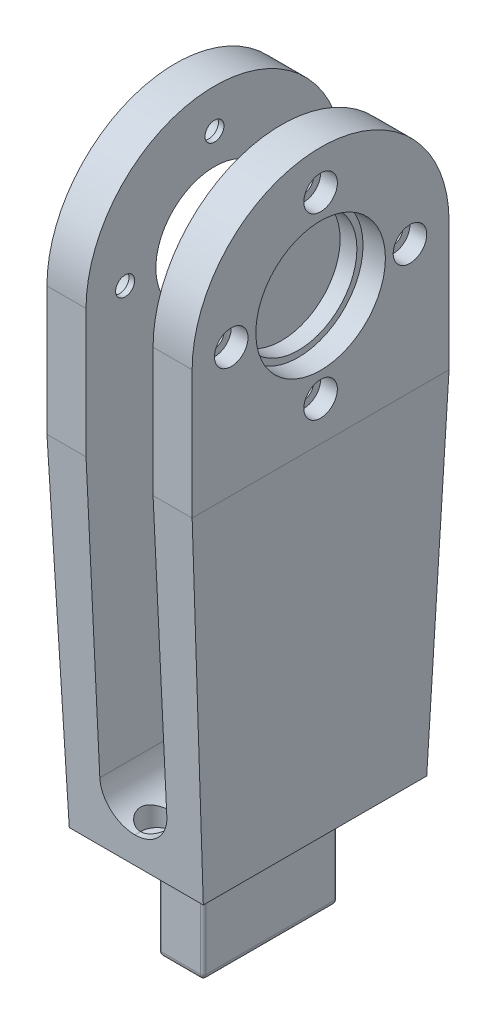
SolidWorks part; units mm, degrees
ref_plane "Front Plane" through (0, 0, 0) normal (0, 0, 1) x (1, 0, 0)
ref_plane "Top Plane" through (0, 0, 0) normal (0, 1, 0) x (1, 0, 0)
ref_plane "Right Plane" through (0, 0, 0) normal (1, 0, 0) x (0, 0, -1)
ref_plane "Plane1" through (6, 0, 0) normal (1, 0, 0) x (0, 0, -1)
sketch "Sketch2" plane through (6, 0, 0) normal (1, 0, 0) x (0, 0, -1)
  line L0 (0, 16) -> (0, 0) construction
  circle A0 centre (0, 0) radius 23
  circle A1 centre (0, 16) radius 1.7
  circle A2 centre (16, 0) radius 1.7
  circle A3 centre (0, -16) radius 1.7
  circle A4 centre (-16, 0) radius 1.7
  point P14 (0, 0)
  dimension "D1" = 46
  dimension "D2" = 3.4
  dimension "D3" = 16
  dimension "D4" = 4
extrude "Boss-Extrude1" add sketch "Sketch2" along normal blind 7
ref_plane "Plane2" through (0, -23, 0) normal (0, -1, 0) x (-1, 0, 0)
sketch "Sketch7" plane through (0, -23, 0) normal (0, -1, 0) x (-1, 0, 0)
  line L0 (-13, -23) -> (-6, -23) construction
  line L1 (-6, -23) -> (-6, 23) construction
  line L2 (-6, 23) -> (-13, 23) construction
  line L4 (-13, -23) -> (-6, -23)
  line L5 (-6, -23) -> (-6, 23)
  line L6 (-6, 23) -> (-13, 23)
  line L8 (-13, 23) -> (-13, -23)
  dimension "D1" = 7
ref_plane "Plane3" through (0, -85, 0) normal (0, 1, 0) x (1, 0, 0)
sketch "Sketch8" plane through (0, -85, 0) normal (0, 1, 0) x (1, 0, 0)
  line L0 (0, 0) -> (-31.8986, 0) construction
  line L2 (6, 20) -> (12, 20)
  line L3 (6, 20) -> (6, -20)
  line L4 (6, -20) -> (12, -20)
  line L5 (12, 20) -> (12, -20)
  line L6 (6, 20) -> (12, -20) construction
  line L7 (6, -20) -> (12, 20) construction
  line L8 (6, -23) -> (6, 23) construction
  point P3 (9, 0)
  dimension "D1" = 6
  dimension "D2" = 40
loft "Loft2" add profiles "Sketch7", "Sketch8"
sketch "Sketch16" plane through (0, -23, 0) normal (0, 1, 0) x (1, 0, 0)
  line L4 (6, 23) -> (6, -23)
  line L5 (6, -23) -> (13, -23)
  line L6 (13, -23) -> (13, 23)
  line L7 (13, 23) -> (6, 23)
  line L8 (6, 23) -> (6, -23)
  line L9 (6, -23) -> (13, -23)
  line L10 (13, -23) -> (13, 23)
  line L11 (13, 23) -> (6, 23)
  dimension "D1" = 0
extrude "Boss-Extrude7" add sketch "Sketch16" along normal up to surface up to face at (13, 0, -23)
sketch "Sketch19" plane through (6, 0, 0) normal (-1, 0, 0) x (0, 0, 1)
  line L0 (-20.2419, -80) -> (20.2419, -80)
  line L1 (-23, -23) -> (-20, -85) construction
  line L2 (23, -23) -> (20, -85) construction
  line L3 (-20, -85) -> (20, -85) construction
  line L4 (20.2419, -80) -> (20, -85)
  line L5 (-20.2419, -80) -> (-20, -85)
  line L6 (-20, -85) -> (20, -85)
  dimension "D1" = 5
extrude "Boss-Extrude8" add sketch "Sketch19" along normal up to surface (6 mm away) up to plane "Right Plane"
sketch "Sketch20" plane through (13, 0, 0) normal (1, 0, 0) x (0, 0, -1)
  circle A0 centre (0, 0) radius 11.6
  dimension "D1" = 23.2
extrude "Cut-Extrude1" cut sketch "Sketch20" against normal blind 4
sketch "Sketch21" plane through (9, 0, 0) normal (1, 0, 0) x (0, 0, -1)
  circle A0 centre (0, 0) radius 10.5
  dimension "D1" = 21
extrude "Cut-Extrude2" cut sketch "Sketch21" against normal through all
mirror "Mirror2" about plane through (0, 0, 0) normal (1, 0, 0) of "Cut-Extrude2", "Cut-Extrude1", "Boss-Extrude8", "Boss-Extrude7", "Loft2", "Boss-Extrude1"
sketch "Sketch22" plane through (-13, 0, 0) normal (-1, 0, 0) x (0, 0, 1)
  circle A0 centre (0, 16) radius 2.3
  circle A1 centre (16, 0) radius 2.3
  circle A2 centre (0, -16) radius 2.3
  circle A3 centre (-16, 0) radius 2.3
  dimension "D1" = 4.6
extrude "Cut-Extrude3" cut sketch "Sketch22" against normal blind 6
sketch "Sketch23" plane through (13, 0, 0) normal (1, 0, 0) x (0, 0, -1)
  circle A0 centre (0, 16) radius 3
  circle A1 centre (16, 0) radius 3
  circle A2 centre (0, -16) radius 3
  circle A3 centre (-16, 0) radius 3
  dimension "D1" = 6
extrude "Cut-Extrude4" cut sketch "Sketch23" against normal blind 3
sketch "Sketch24" plane through (0, -85, 0) normal (0, -1, 0) x (1, 0, 0)
  line L44 (-4, -12) -> (4, -12)
  line L45 (4, -12) -> (4, 12)
  line L46 (4, 12) -> (-4, 12)
  line L47 (-4, 12) -> (-4, -12)
  line L48 (-4, -12) -> (4, -12)
  line L49 (4, -12) -> (4, 12)
  line L50 (4, 12) -> (-4, 12)
  line L51 (-4, 12) -> (-4, -12)
  dimension "D1" = 8
extrude "Boss-Extrude9" add sketch "Sketch24" along normal blind 20
fillet "Fillet1" radius 1 4 edges at (0, -105, 12) (4, -105, 0) (0, -105, -12) (-4, -105, 0)
fillet "Fillet2" radius 0.5 8 edges at (-3.7071, -104.7071, -11.7071) (3.7071, -104.7071, -11.7071) (-3.7071, -104.7071, 11.7071) (3.7071, -104.7071, 11.7071) (-4, -94.5, -12) (4, -94.5, -12) (-4, -94.5, 12) (4, -94.5, 12)
sketch "Sketch25" plane through (0, -80, 0) normal (0, 1, 0) x (1, 0, 0)
  line L0 (0, 19.2419) -> (2.2364, 19.2419) construction
  line L1 (-6, 20.2419) -> (6, 20.2419) construction
  line L2 (0, 16.2419) -> (0, 0) construction
  line L3 (0, 0) -> (6, 0) construction
  line L4 (6, -20.2419) -> (6, 20.2419) construction
  circle A0 centre (0, 16.2419) radius 1.7
  circle A1 centre (0, 16.2419) radius 3 construction
  circle A2 centre (0, -16.2419) radius 1.7
  dimension "D1" = 3.4
  dimension "D2" = 6
  dimension "D3" = 1
extrude "Cut-Extrude5" cut sketch "Sketch25" against normal through all
sketch "Sketch26" plane through (0, -80, 0) normal (0, 1, 0) x (1, 0, 0)
  circle A0 centre (0, 16.2419) radius 3
  circle A1 centre (0, -16.2419) radius 3
  dimension "D1" = 6
extrude "Cut-Extrude6" cut sketch "Sketch26" against normal blind 3
fillet "Fillet3" radius 6 2 edges at (-6, -80, 0) (6, -80, 0)
